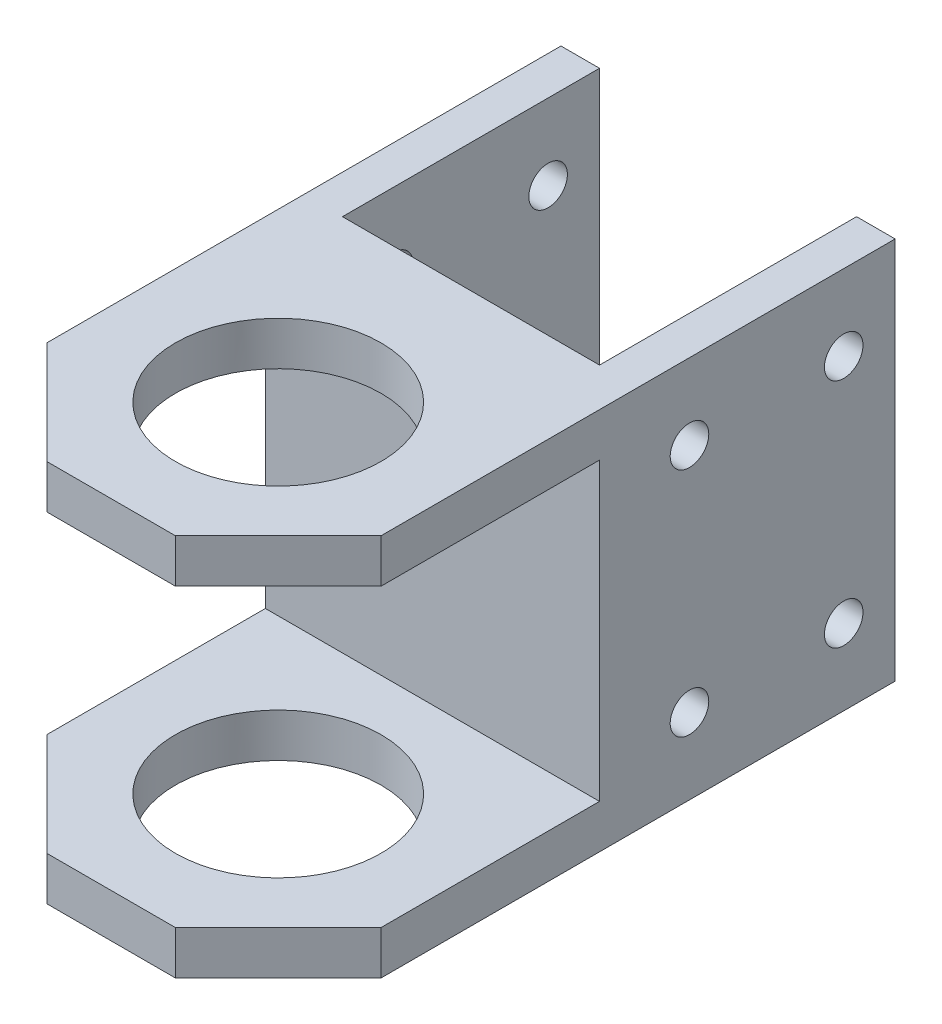
SolidWorks part; units mm, degrees
material "1060 合金"
ref_plane "前视基准面" through (0, 0, 0) normal (0, 0, 1) x (1, 0, 0)
ref_plane "上视基准面" through (0, 0, 0) normal (0, 1, 0) x (1, 0, 0)
ref_plane "右视基准面" through (0, 0, 0) normal (1, 0, 0) x (0, 0, -1)
sketch "草图1" plane through (0, 0, 0) normal (0, 0, 1) x (1, 0, 0)
  line L1 (-13, -10) -> (13, -10)
  line L2 (-13, -10) -> (-13, 10)
  line L3 (-13, 10) -> (13, 10)
  line L4 (13, -10) -> (13, 10)
  line L5 (-13, -10) -> (13, 10) construction
  line L6 (-13, 10) -> (13, -10) construction
  point P0 (0, 0)
  dimension "D1" = 20
  dimension "D2" = 26
extrude "凸台-拉伸1" add sketch "草图1" along normal blind 3
sketch "草图2" plane through (0, -10, 0) normal (0, -1, 0) x (1, 0, 0)
  line L0 (-13, 3) -> (-13, 15)
  line L1 (-13, 15) -> (-13, 28)
  line L2 (-13, 28) -> (13, 28)
  line L3 (13, 15) -> (13, 3)
  line L4 (13, 28) -> (13, 15)
  line L5 (13, 3) -> (-13, 3)
  line L6 (13, 3) -> (13, 0) construction
  arc A0 (13, 15) -> (-13, 15) centre (0, 15) ccw construction
  dimension "D1" = 26
  dimension "D2" = 12
extrude "凸台-拉伸2" add sketch "草图2" against normal blind 16
sketch "草图3" plane through (0, -10, 0) normal (0, -1, 0) x (1, 0, 0)
  line L0 (-13, 0) -> (13, 0) construction
  circle A0 centre (0, 15) radius 9
  dimension "D1" = 18
  dimension "D2" = 15
sketch "草图5" plane through (0, 0, 0) normal (0, 0, -1) x (-1, 0, 0)
  line L1 (13, -10) -> (10, -10)
  line L2 (13, -10) -> (13, 10)
  line L3 (13, 10) -> (10, 10)
  line L4 (10, -10) -> (10, 10)
  line L5 (-13, 10) -> (13, 10) construction
  line L7 (-13, -10) -> (-10, -10)
  line L8 (-13, -10) -> (-13, 10)
  line L9 (-13, 10) -> (-10, 10)
  line L10 (-10, -10) -> (-10, 10)
  dimension "D2" = 3
  dimension "D4" = 3
extrude "凸台-拉伸3" add sketch "草图5" along normal blind 20
sketch "草图8" plane through (13, 0, 0) normal (1, 0, 0) x (0, 0, -1)
  line L1 (-26, -6) -> (-3, -6)
  line L2 (-26, -6) -> (-26, 2)
  line L3 (-26, 2) -> (-3, 2)
  line L4 (-3, -6) -> (-3, 2)
  line L5 (-28, -10) -> (20, -10) construction
  line L6 (-3, 6) -> (-3, 10) construction
  dimension "D1" = 23
  dimension "D2" = 4
  dimension "D3" = 8
extrude "切除-拉伸5" cut sketch "草图8" against normal blind 40
chamfer "倒角1" distance 8 angle 45 2 edges at (-13, -2, 28) (13, -2, 28)
sketch "草图16" plane through (13, 0, 0) normal (1, 0, 0) x (0, 0, -1)
  line L1 (-3, 6) -> (20, 6)
  line L2 (-3, 6) -> (-3, 10)
  line L3 (-3, 10) -> (20, 10)
  line L4 (20, 6) -> (20, 10)
extrude "切除-拉伸8" cut sketch "草图16" against normal up to surface (26 mm away) up to face at (-13, 0.6, 6.05)
sketch "草图17" plane through (0, 0, 28) normal (0, 0, 1) x (1, 0, 0)
  line L0 (0.1863, 6) -> (0, -10) construction
  line L1 (5, 6) -> (-5, 6) construction
  line L2 (5, -10) -> (-5, -10) construction
  line L4 (-8.3533, -6) -> (8.5396, -6)
  line L5 (-8.3533, -6) -> (-8.3533, 2)
  line L6 (-8.3533, 2) -> (8.5396, 2)
  line L7 (8.5396, -6) -> (8.5396, 2)
  line L8 (-8.3533, -6) -> (8.5396, 2) construction
  line L9 (-8.3533, 2) -> (8.5396, -6) construction
  point P6 (0.0932, -2)
  dimension "D1" = 8
  dimension "D2" = 16.8929
extrude "切除-拉伸9" cut sketch "草图17" against normal blind 10
sketch "草图18" plane through (0, -10, 0) normal (0, -1, 0) x (1, 0, 0)
  line L10 (5, 28) -> (-5, 28)
  line L11 (-5, 28) -> (-13, 20)
  line L12 (-13, 20) -> (-13, -20)
  line L13 (-13, -20) -> (-10, -20)
  line L14 (-10, -20) -> (-10, 0)
  line L15 (-10, 0) -> (10, 0)
  line L16 (10, 0) -> (10, -20)
  line L17 (10, -20) -> (13, -20)
  line L18 (13, -20) -> (13, 20)
  line L19 (13, 20) -> (5, 28)
  line L20 (5, 28) -> (-5, 28)
  line L21 (-5, 28) -> (-13, 20)
  line L22 (-13, 20) -> (-13, -20)
  line L23 (-13, -20) -> (-10, -20)
  line L24 (-10, -20) -> (-10, 0)
  line L25 (-10, 0) -> (10, 0)
  line L26 (10, 0) -> (10, -20)
  line L27 (10, -20) -> (13, -20)
  line L28 (13, -20) -> (13, 20)
  line L29 (13, 20) -> (5, 28)
  dimension "D1" = 0
extrude "凸台-拉伸4" add sketch "草图18" along normal blind 14
sketch "草图19" plane through (0, -6, 0) normal (0, 1, 0) x (1, 0, 0)
  line L6 (5, -28) -> (13, -20)
  line L7 (13, -20) -> (13, -3)
  line L8 (13, -3) -> (-13, -3)
  line L9 (-13, -3) -> (-13, -20)
  line L10 (-13, -20) -> (-5, -28)
  line L11 (-5, -28) -> (5, -28)
  line L12 (5, -28) -> (13, -20)
  line L13 (13, -20) -> (13, -3)
  line L14 (13, -3) -> (-13, -3)
  line L15 (-13, -3) -> (-13, -20)
  line L16 (-13, -20) -> (-5, -28)
  line L17 (-5, -28) -> (5, -28)
  dimension "D1" = 0
extrude "切除-拉伸10" cut sketch "草图19" against normal blind 14
sketch "草图20" plane through (0, -24, 0) normal (0, -1, 0) x (1, 0, 0)
  circle A0 centre (0, 15) radius 8
extrude "切除-拉伸11" cut sketch "草图20" against normal blind 39
sketch "草图21" plane through (0, -24, 0) normal (0, -1, 0) x (1, 0, 0)
  circle A0 centre (0, 15) radius 9
extrude "切除-拉伸12" cut sketch "草图21" against normal blind 0.1
sketch "草图22" plane through (0, 6, 0) normal (0, 1, 0) x (1, 0, 0)
  circle A0 centre (0, -15) radius 9
extrude "切除-拉伸13" cut sketch "草图22" against normal blind 0.1
sketch "草图23" plane through (13, 0, 0) normal (1, 0, 0) x (0, 0, -1)
  line L0 (20, -9) -> (10, -9) construction
  line L1 (20, 6) -> (20, -24) construction
  line L3 (4, -18) -> (16, -18) construction
  line L4 (4, -18) -> (4, 0) construction
  line L5 (4, 0) -> (16, 0) construction
  line L6 (16, -18) -> (16, 0) construction
  line L7 (4, -18) -> (16, 0) construction
  line L8 (4, 0) -> (16, -18) construction
  circle A0 centre (4, 0) radius 1.5
  circle A1 centre (16, 0) radius 1.5
  circle A2 centre (4, -18) radius 1.5
  circle A3 centre (16, -18) radius 1.5
  dimension "D1" = 18
  dimension "D2" = 12
extrude "切除-拉伸14" cut sketch "草图23" against normal blind 38.1
sketch "草图24" plane through (0, 2, 0) normal (0, -1, 0) x (1, 0, 0)
  line L6 (-5, 28) -> (-13, 20)
  line L7 (-13, 20) -> (-13, 3)
  line L8 (-13, 3) -> (13, 3)
  line L9 (13, 3) -> (13, 20)
  line L10 (13, 20) -> (5, 28)
  line L11 (5, 28) -> (-5, 28)
  line L12 (-5, 28) -> (-13, 20)
  line L13 (-13, 20) -> (-13, 3)
  line L14 (-13, 3) -> (13, 3)
  line L15 (13, 3) -> (13, 20)
  line L16 (13, 20) -> (5, 28)
  line L17 (5, 28) -> (-5, 28)
  dimension "D1" = 0
extrude "切除-拉伸15" cut sketch "草图24" against normal blind 0.5
sketch "草图25" plane through (0, -20, 0) normal (0, 1, 0) x (1, 0, 0)
  line L6 (-5, -28) -> (5, -28)
  line L7 (5, -28) -> (13, -20)
  line L8 (13, -20) -> (13, -3)
  line L9 (13, -3) -> (-13, -3)
  line L10 (-13, -3) -> (-13, -20)
  line L11 (-13, -20) -> (-5, -28)
  line L12 (-5, -28) -> (5, -28)
  line L13 (5, -28) -> (13, -20)
  line L14 (13, -20) -> (13, -3)
  line L15 (13, -3) -> (-13, -3)
  line L16 (-13, -3) -> (-13, -20)
  line L17 (-13, -20) -> (-5, -28)
  dimension "D1" = 0
extrude "切除-拉伸16" cut sketch "草图25" against normal blind 0.5
sketch "草图26" plane through (0, -24, 0) normal (0, -1, 0) x (1, 0, 0)
  line L10 (13, 20) -> (5, 28)
  line L11 (5, 28) -> (-5, 28)
  line L12 (-5, 28) -> (-13, 20)
  line L13 (-13, 20) -> (-13, -20)
  line L14 (-13, -20) -> (-10, -20)
  line L15 (-10, -20) -> (-10, 0)
  line L16 (-10, 0) -> (10, 0)
  line L17 (10, 0) -> (10, -20)
  line L18 (10, -20) -> (13, -20)
  line L19 (13, -20) -> (13, 20)
  line L20 (13, 20) -> (5, 28)
  line L21 (5, 28) -> (-5, 28)
  line L22 (-5, 28) -> (-13, 20)
  line L23 (-13, 20) -> (-13, -20)
  line L24 (-13, -20) -> (-10, -20)
  line L25 (-10, -20) -> (-10, 0)
  line L26 (-10, 0) -> (10, 0)
  line L27 (10, 0) -> (10, -20)
  line L28 (10, -20) -> (13, -20)
  line L29 (13, -20) -> (13, 20)
  dimension "D1" = 0
extrude "切除-拉伸17" cut sketch "草图26" against normal blind 0.1
sketch "草图27" plane through (0, 6, 0) normal (0, 1, 0) x (1, 0, 0)
  line L10 (-13, 20) -> (-13, -20)
  line L11 (-13, -20) -> (-5, -28)
  line L12 (-5, -28) -> (5, -28)
  line L13 (5, -28) -> (13, -20)
  line L14 (13, -20) -> (13, 20)
  line L15 (13, 20) -> (10, 20)
  line L16 (10, 20) -> (10, 0)
  line L17 (10, 0) -> (-10, 0)
  line L18 (-10, 0) -> (-10, 20)
  line L19 (-10, 20) -> (-13, 20)
  line L20 (-13, 20) -> (-13, -20)
  line L21 (-13, -20) -> (-5, -28)
  line L22 (-5, -28) -> (5, -28)
  line L23 (5, -28) -> (13, -20)
  line L24 (13, -20) -> (13, 20)
  line L25 (13, 20) -> (10, 20)
  line L26 (10, 20) -> (10, 0)
  line L27 (10, 0) -> (-10, 0)
  line L28 (-10, 0) -> (-10, 20)
  line L29 (-10, 20) -> (-13, 20)
  dimension "D1" = 0
extrude "切除-拉伸18" cut sketch "草图27" against normal blind 0.1
